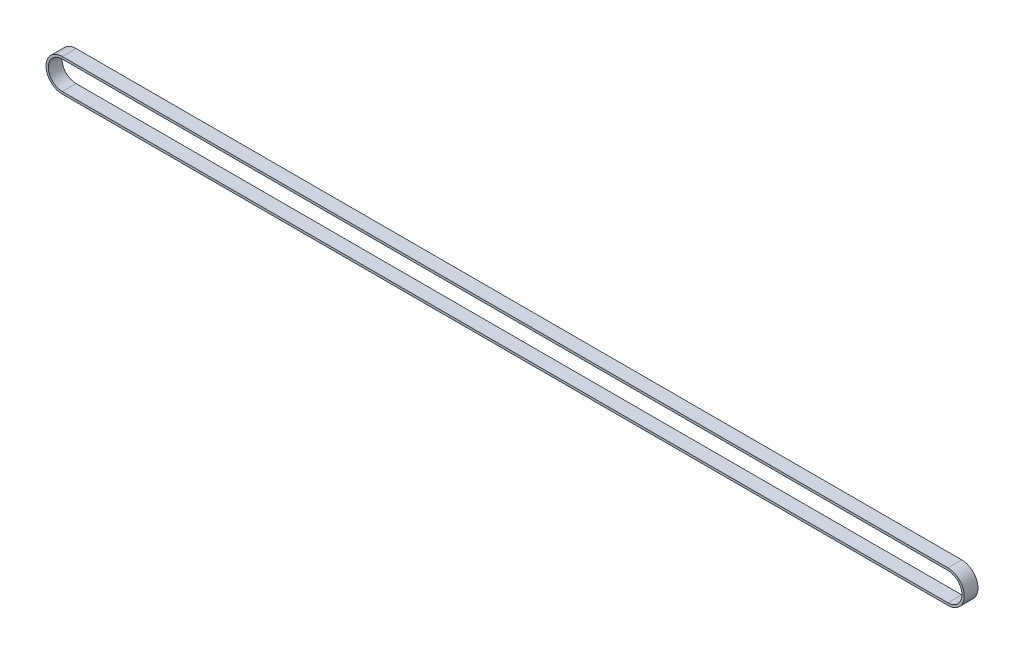
SolidWorks part; units mm, degrees
ref_plane "Front Plane" through (0, 0, 0) normal (0, 0, 1) x (1, 0, 0)
ref_plane "Top Plane" through (0, 0, 0) normal (0, 1, 0) x (1, 0, 0)
ref_plane "Right Plane" through (0, 0, 0) normal (1, 0, 0) x (0, 0, -1)
sketch "Sketch2" plane through (0, 0, 0) normal (0, 0, 1) x (1, 0, 0)
  line L0 (192.875, -6.1) -> (0, -6.1)
  line L1 (0, 6.1) -> (192.875, 6.1)
  line L2 (192.875, 6.1) -> (192.875, -6.1) construction
  arc A0 (0, -6.1) -> (0, 6.1) centre (0, 0) cw
  dimension "D1" = 6.1
  dimension "D2" = 192.875
extrude "Extrude-Thin1" add sketch "Sketch2" along normal blind 6 thin thin type one direction reverse wall 1
mirror "Mirror1" about plane through (192.875, 7.1, 6) normal (1, 0, 0) of "Extrude-Thin1"
equation "\"D2@Sketch2\"=385.75 / 2"
